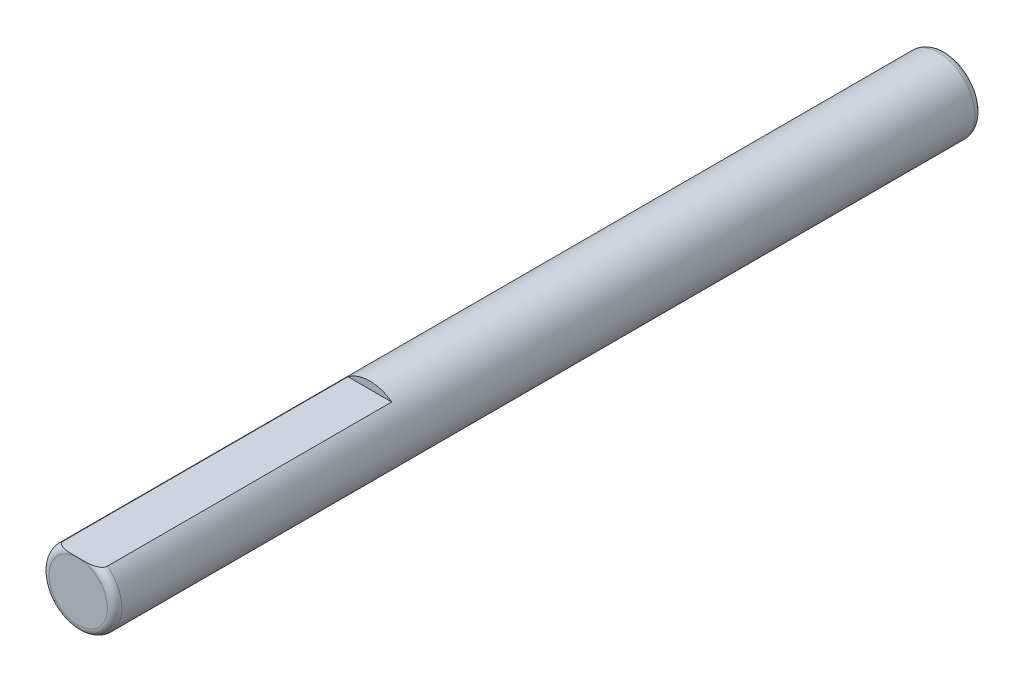
SolidWorks part; units mm, degrees
ref_plane "Front Plane" through (0, 0, 0) normal (0, 0, 1) x (1, 0, 0)
ref_plane "Top Plane" through (0, 0, 0) normal (0, 1, 0) x (1, 0, 0)
ref_plane "Right Plane" through (0, 0, 0) normal (1, 0, 0) x (0, 0, -1)
sketch "Sketch1" plane through (0, 0, 0) normal (0, 0, 1) x (1, 0, 0)
  circle A0 centre (0, 0) radius 2.5
  dimension "D1" = 5
extrude "Boss-Extrude1" add sketch "Sketch1" along normal mid plane 59.5
sketch "Sketch2" plane through (0, 0, 29.75) normal (0, 0, 1) x (1, 0, 0)
  line L0 (-1.5, 2) -> (1.5, 2)
  line L1 (0, 0) -> (0, 1.0756) construction
  circle A1 centre (0, 0) radius 2.5
  arc A2 (-1.5, 2) -> (1.5, 2) centre (0, 0) ccw
  point P2 (0, 0)
  circle M4 centre (0, 0) radius 2.5
  dimension "D2" = 2
  dimension "D1" = 0
extrude "Cut-Extrude2" cut sketch "Sketch2" against normal blind 20 contours L0 L1 M4 | L1 L0 M4 region at (0, 2.2018, 29.75)
fillet "Fillet1" radius 0.5 2 edges at (2.5, 0, -29.75) (0, -2.5, 29.75)
